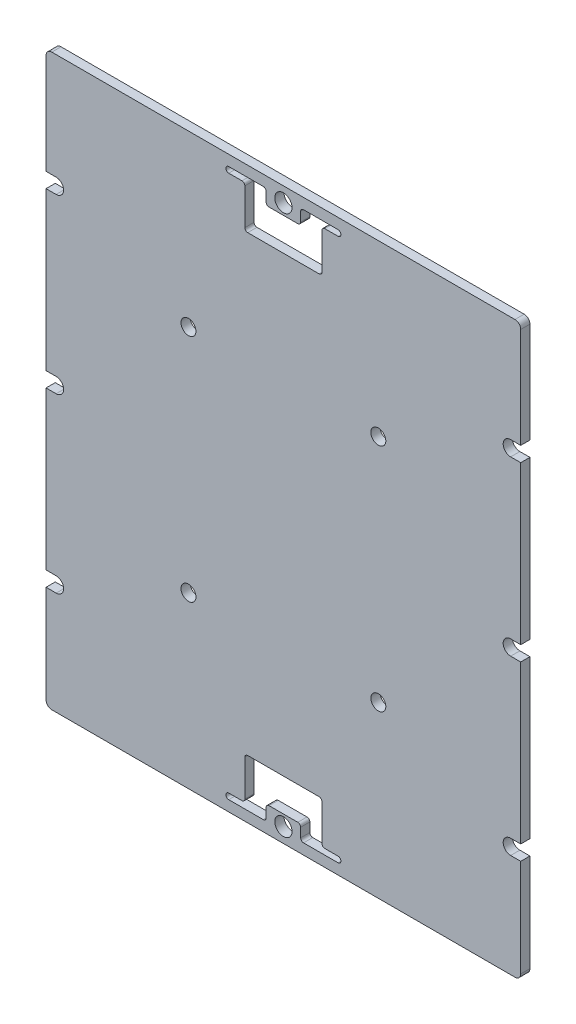
SolidWorks part; units mm, degrees
material "FR4_stuffedProtoboard"
ref_plane "Front Plane" through (0, 0, 0) normal (0, 0, 1) x (1, 0, 0)
ref_plane "Top Plane" through (0, 0, 0) normal (0, 1, 0) x (1, 0, 0)
ref_plane "Right Plane" through (0, 0, 0) normal (1, 0, 0) x (0, 0, -1)
sketch "Sketch2" plane through (0, 0, 0) normal (0, 0, 1) x (1, 0, 0)
  line L0 (39.5, 49.75) -> (-39.5, 49.75) construction
  line L1 (-41.5, 49.75) -> (41.5, 49.75) construction
  line L2 (-41.5, 49.75) -> (-41.5, -49.75) construction
  line L3 (-41.5, -49.75) -> (41.5, -49.75) construction
  line L4 (41.5, 49.75) -> (41.5, -49.75) construction
  line L5 (-41.5, 49.75) -> (41.5, -49.75) construction
  line L6 (-41.5, -49.75) -> (41.5, 49.75) construction
  line L7 (41.5, 51.75) -> (41.5, 40.35) construction
  line L8 (-41.5, 49.75) -> (41.5, 49.75) construction
  line L9 (41.5, 49.75) -> (41.5, -49.75) construction
  line L10 (-41.5, -49.75) -> (41.5, -49.75) construction
  line L11 (-41.5, 49.75) -> (-41.5, -49.75) construction
  line L12 (-37, -31.85) -> (37, -31.85) construction
  line L13 (-37, -30.25) -> (37, -30.25) construction
  line L14 (-37, -21.85) -> (37, -21.85) construction
  line L15 (-37, -20.25) -> (37, -20.25) construction
  line L16 (-37, -11.85) -> (37, -11.85) construction
  line L17 (-37, -10.25) -> (37, -10.25) construction
  line L18 (-37, -1.85) -> (37, -1.85) construction
  line L19 (-37, -0.25) -> (37, -0.25) construction
  line L20 (-37, 8.15) -> (37, 8.15) construction
  line L21 (-37, 9.75) -> (37, 9.75) construction
  line L22 (-37, 18.15) -> (37, 18.15) construction
  line L23 (-37, 19.75) -> (37, 19.75) construction
  line L24 (-37, 28.15) -> (37, 28.15) construction
  line L25 (-37, 29.75) -> (37, 29.75) construction
  line L26 (-37, 38.15) -> (37, 38.15) construction
  line L27 (-37, 39.75) -> (37, 39.75) construction
  line L28 (-37, -31.85) -> (37, -31.85) construction
  line L29 (-37, -30.25) -> (37, -30.25) construction
  line L30 (-37, -21.85) -> (37, -21.85) construction
  line L31 (-37, -20.25) -> (37, -20.25) construction
  line L32 (-37, -11.85) -> (37, -11.85) construction
  line L33 (-37, -10.25) -> (37, -10.25) construction
  line L34 (-37, -1.85) -> (37, -1.85) construction
  line L35 (-37, -0.25) -> (37, -0.25) construction
  line L36 (-37, 8.15) -> (37, 8.15) construction
  line L37 (-37, 9.75) -> (37, 9.75) construction
  line L38 (-37, 18.15) -> (37, 18.15) construction
  line L39 (-37, 19.75) -> (37, 19.75) construction
  line L40 (-37, 28.15) -> (37, 28.15) construction
  line L41 (-37, 29.75) -> (37, 29.75) construction
  line L42 (-37, 38.15) -> (37, 38.15) construction
  line L43 (-37, 39.75) -> (37, 39.75) construction
  line L44 (-37, -40.25) -> (37, -40.25) construction
  line L45 (-37, -41.85) -> (37, -41.85) construction
  line L46 (-41.5, 51.75) -> (-41.5, 40.35) construction
  line L47 (39.5, -49.75) -> (-39.5, -49.75) construction
  line L48 (41.5, -31.9) -> (41.5, -51.75) construction
  line L49 (-41.25, 49.5) -> (41.25, 49.5)
  line L50 (41.25, 49.5) -> (41.25, -49.5)
  line L51 (-41.25, -49.5) -> (41.25, -49.5)
  line L52 (-41.25, 49.5) -> (-41.25, -49.5)
  circle A0 centre (0, 46.95) radius 1.5 construction
  circle A1 centre (0, 46.95) radius 0.8 construction
  circle A2 centre (0, 46.95) radius 1.5 construction
  circle A3 centre (0, 46.95) radius 0.8
  circle A4 centre (-39.5, -30.25) radius 0.8 construction
  circle A5 centre (-39.5, -0.25) radius 0.8 construction
  circle A6 centre (-39.5, 29.75) radius 0.8 construction
  circle A7 centre (-39.5, -30.25) radius 0.8
  circle A8 centre (-39.5, -0.25) radius 0.8
  circle A9 centre (-39.5, 29.75) radius 0.8
  circle A10 centre (39.5, -30.25) radius 0.8 construction
  circle A11 centre (39.5, -0.25) radius 0.8 construction
  circle A12 centre (39.5, 29.75) radius 0.8 construction
  circle A13 centre (39.5, -30.25) radius 0.8
  circle A14 centre (39.5, -0.25) radius 0.8
  circle A15 centre (39.5, 29.75) radius 0.8
  circle A16 centre (0, -46.95) radius 0.8 construction
  circle A17 centre (0, -46.95) radius 0.8
  circle A18 centre (0, -46.95) radius 1.5 construction
  circle A19 centre (0, -46.95) radius 1.5
  circle A20 centre (-16.5, 20) radius 1.75 construction
  circle A21 centre (-16.5, 20) radius 0.8 construction
  circle A22 centre (-16.5, 20) radius 1.75 construction
  circle A23 centre (-16.5, 20) radius 0.8
  circle A24 centre (16.5, 20) radius 1.75 construction
  circle A25 centre (16.5, 20) radius 0.8 construction
  circle A26 centre (16.5, 20) radius 1.75 construction
  circle A27 centre (16.5, 20) radius 0.8
  circle A28 centre (16.5, -20) radius 1.75 construction
  circle A29 centre (-16.5, -20) radius 1.75 construction
  circle A30 centre (16.5, -20) radius 1.75 construction
  circle A31 centre (-16.5, -20) radius 1.75 construction
  circle A32 centre (-16.5, -20) radius 0.8 construction
  circle A33 centre (-16.5, -20) radius 0.8
  circle A34 centre (16.5, -20) radius 0.8 construction
  circle A35 centre (16.5, -20) radius 0.8
  point P0 (0, 0)
  point P74 (0, -40.25)
  point P75 (0, -31.85)
  point P76 (0, -41.85)
  dimension "D2" = 10
  dimension "D3" = 1.6
  dimension "D1" = 0.25
extrude "pcb extrude" add sketch "Sketch2" along normal mid plane 1.6 contours L4 L1 L2 L3 A2 | A2 A3 | L2 L1 L4 L3 region at (0, 0.0296, 0)
sketch "connector locations" plane through (0, 0, 0.8) normal (0, 0, 1) x (1, 0, 0)
  line L0 (34.5, 45.75) -> (4.5, 45.75) construction
  line L1 (-2.5, 44.75) -> (2.5, 44.75) construction
  line L2 (-4.5, 45.75) -> (-34.5, 45.75) construction
  line L3 (34.5, 45.75) -> (4.5, 45.75)
  line L4 (-2.5, 44.75) -> (2.5, 44.75)
  line L5 (-4.5, 45.75) -> (-34.5, 45.75)
  line L6 (-37, 43.25) -> (-37, -43.25) construction
  line L7 (-37, 43.25) -> (-37, -43.25)
  line L8 (37, -43.25) -> (37, 43.25) construction
  line L9 (37, -43.25) -> (37, 43.25)
  line L10 (4.5, -45.75) -> (34.5, -45.75) construction
  line L11 (4.5, -45.75) -> (34.5, -45.75)
  line L12 (-34.5, -45.75) -> (-4.5, -45.75) construction
  line L13 (-2.5, -44.75) -> (2.5, -44.75) construction
  line L14 (-34.5, -45.75) -> (-4.5, -45.75)
  line L15 (-2.5, -44.75) -> (2.5, -44.75)
  line L16 (-37, 39.75) -> (37, 39.75) construction
  line L17 (-33.9182, 41.909) -> (-9.2802, 41.909)
  line L18 (-33.9182, 41.909) -> (-33.9182, 43.306)
  line L19 (-33.9182, 43.306) -> (-9.2802, 43.306)
  line L20 (-9.2802, 41.909) -> (-9.2802, 43.306)
  line L21 (-33.9182, 41.909) -> (-9.2802, 43.306) construction
  line L22 (-33.9182, 43.306) -> (-9.2802, 41.909) construction
  line L23 (-33.9182, 33.306) -> (-22.0818, 33.306)
  line L24 (-33.9182, 33.306) -> (-33.9182, 31.909)
  line L25 (-33.9182, 31.909) -> (-22.0818, 31.909)
  line L26 (-22.0818, 33.306) -> (-22.0818, 31.909)
  line L27 (-33.9182, 33.306) -> (-22.0818, 31.909) construction
  line L28 (-33.9182, 31.909) -> (-22.0818, 33.306) construction
  line L29 (-12.319, 33.306) -> (12.319, 33.306)
  line L30 (-12.319, 33.306) -> (-12.319, 31.909)
  line L31 (-12.319, 31.909) -> (12.319, 31.909)
  line L32 (12.319, 33.306) -> (12.319, 31.909)
  line L33 (-12.319, 33.306) -> (12.319, 31.909) construction
  line L34 (-12.319, 31.909) -> (12.319, 33.306) construction
  line L35 (-33.9182, 23.306) -> (-22.0818, 23.306)
  line L36 (-33.9182, 23.306) -> (-33.9182, 21.909)
  line L37 (-33.9182, 21.909) -> (-22.0818, 21.909)
  line L38 (-33.9182, 23.306) -> (-22.0818, 21.909) construction
  line L39 (-33.9182, 21.909) -> (-22.0818, 23.306) construction
  line L40 (-22.0818, 23.306) -> (-22.0818, 21.909)
  line L41 (-12.319, 23.306) -> (-12.319, 21.909)
  line L42 (-12.319, 23.306) -> (12.319, 23.306)
  line L43 (-12.319, 21.909) -> (12.319, 21.909)
  line L44 (-12.319, 23.306) -> (12.319, 21.909) construction
  line L45 (-12.319, 21.909) -> (12.319, 23.306) construction
  line L46 (12.319, 23.306) -> (12.319, 21.909)
  line L47 (-33.9182, 13.306) -> (-22.0818, 13.306)
  line L48 (-33.9182, 13.306) -> (-33.9182, 11.909)
  line L49 (-33.9182, 11.909) -> (-22.0818, 11.909)
  line L50 (-33.9182, 13.306) -> (-22.0818, 11.909) construction
  line L51 (-33.9182, 11.909) -> (-22.0818, 13.306) construction
  line L52 (-22.0818, 13.306) -> (-22.0818, 11.909)
  line L53 (-12.319, 13.306) -> (-12.319, 11.909)
  line L54 (-12.319, 13.306) -> (12.319, 13.306)
  line L55 (-12.319, 11.909) -> (12.319, 11.909)
  line L56 (-12.319, 13.306) -> (12.319, 11.909) construction
  line L57 (-12.319, 11.909) -> (12.319, 13.306) construction
  line L58 (12.319, 13.306) -> (12.319, 11.909)
  line L59 (-33.9182, 3.306) -> (-22.0818, 3.306)
  line L60 (-33.9182, 3.306) -> (-33.9182, 1.909)
  line L61 (-33.9182, 1.909) -> (-22.0818, 1.909)
  line L62 (-33.9182, 3.306) -> (-22.0818, 1.909) construction
  line L63 (-33.9182, 1.909) -> (-22.0818, 3.306) construction
  line L64 (-22.0818, 3.306) -> (-22.0818, 1.909)
  line L65 (-12.319, 3.306) -> (-12.319, 1.909)
  line L66 (-12.319, 3.306) -> (12.319, 3.306)
  line L67 (-12.319, 1.909) -> (12.319, 1.909)
  line L68 (-12.319, 3.306) -> (12.319, 1.909) construction
  line L69 (-12.319, 1.909) -> (12.319, 3.306) construction
  line L70 (12.319, 3.306) -> (12.319, 1.909)
  line L71 (-33.9182, -6.694) -> (-22.0818, -6.694)
  line L72 (-33.9182, -6.694) -> (-33.9182, -8.091)
  line L73 (-33.9182, -8.091) -> (-22.0818, -8.091)
  line L74 (-33.9182, -6.694) -> (-22.0818, -8.091) construction
  line L75 (-33.9182, -8.091) -> (-22.0818, -6.694) construction
  line L76 (-22.0818, -6.694) -> (-22.0818, -8.091)
  line L77 (-12.319, -6.694) -> (-12.319, -8.091)
  line L78 (-12.319, -6.694) -> (12.319, -6.694)
  line L79 (-12.319, -8.091) -> (12.319, -8.091)
  line L80 (-12.319, -6.694) -> (12.319, -8.091) construction
  line L81 (-12.319, -8.091) -> (12.319, -6.694) construction
  line L82 (12.319, -6.694) -> (12.319, -8.091)
  line L83 (-33.9182, -16.694) -> (-22.0818, -16.694)
  line L84 (-33.9182, -16.694) -> (-33.9182, -18.091)
  line L85 (-33.9182, -18.091) -> (-22.0818, -18.091)
  line L86 (-33.9182, -16.694) -> (-22.0818, -18.091) construction
  line L87 (-33.9182, -18.091) -> (-22.0818, -16.694) construction
  line L88 (-22.0818, -16.694) -> (-22.0818, -18.091)
  line L89 (-12.319, -16.694) -> (-12.319, -18.091)
  line L90 (-12.319, -16.694) -> (12.319, -16.694)
  line L91 (-12.319, -18.091) -> (12.319, -18.091)
  line L92 (-12.319, -16.694) -> (12.319, -18.091) construction
  line L93 (-12.319, -18.091) -> (12.319, -16.694) construction
  line L94 (12.319, -16.694) -> (12.319, -18.091)
  line L95 (-33.9182, -26.694) -> (-22.0818, -26.694)
  line L96 (-33.9182, -26.694) -> (-33.9182, -28.091)
  line L97 (-33.9182, -28.091) -> (-22.0818, -28.091)
  line L98 (-33.9182, -26.694) -> (-22.0818, -28.091) construction
  line L99 (-33.9182, -28.091) -> (-22.0818, -26.694) construction
  line L100 (-22.0818, -26.694) -> (-22.0818, -28.091)
  line L101 (-12.319, -26.694) -> (-12.319, -28.091)
  line L102 (-12.319, -26.694) -> (12.319, -26.694)
  line L103 (-12.319, -28.091) -> (12.319, -28.091)
  line L104 (-12.319, -26.694) -> (12.319, -28.091) construction
  line L105 (-12.319, -28.091) -> (12.319, -26.694) construction
  line L106 (12.319, -26.694) -> (12.319, -28.091)
  line L111 (-35.52, -38.1) -> (-10.98, -38.1)
  line L116 (-35.52, -38.1) -> (-35.52, -37.9)
  line L117 (-35.52, -37.9) -> (-10.98, -37.9)
  line L119 (0, 32.6075) -> (0, 22.6075) construction
  line L120 (-37, 29.75) -> (37, 29.75) construction
  line L121 (32.92, 41.02) -> (35.08, 38.84) construction
  line L122 (32.92, 38.84) -> (35.08, 41.02) construction
  line L123 (26.92, 38.84) -> (29.08, 41.02) construction
  line L124 (26.92, 41.02) -> (29.08, 38.84) construction
  line L125 (20.92, 38.84) -> (23.08, 41.02) construction
  line L126 (20.92, 41.02) -> (23.08, 38.84) construction
  line L127 (26.92, 28.84) -> (29.08, 31.02) construction
  line L128 (26.92, 31.02) -> (29.08, 28.84) construction
  line L129 (20.92, 28.84) -> (23.08, 31.02) construction
  line L130 (20.92, 31.02) -> (23.08, 28.84) construction
  line L131 (26.92, 18.84) -> (29.08, 21.02) construction
  line L132 (26.92, 21.02) -> (29.08, 18.84) construction
  line L133 (20.92, 18.84) -> (23.08, 21.02) construction
  line L134 (20.92, 21.02) -> (23.08, 18.84) construction
  line L135 (26.92, 8.84) -> (29.08, 11.02) construction
  line L136 (26.92, 11.02) -> (29.08, 8.84) construction
  line L137 (20.92, 8.84) -> (23.08, 11.02) construction
  line L138 (20.92, 11.02) -> (23.08, 8.84) construction
  line L139 (26.92, -1.16) -> (29.08, 1.02) construction
  line L140 (26.92, 1.02) -> (29.08, -1.16) construction
  line L141 (20.92, -1.16) -> (23.08, 1.02) construction
  line L142 (20.92, 1.02) -> (23.08, -1.16) construction
  line L143 (26.92, -11.16) -> (29.08, -8.98) construction
  line L144 (26.92, -8.98) -> (29.08, -11.16) construction
  line L145 (20.92, -11.16) -> (23.08, -8.98) construction
  line L146 (20.92, -8.98) -> (23.08, -11.16) construction
  line L147 (26.92, -21.16) -> (29.08, -18.98) construction
  line L148 (26.92, -18.98) -> (29.08, -21.16) construction
  line L149 (20.92, -21.16) -> (23.08, -18.98) construction
  line L150 (20.92, -18.98) -> (23.08, -21.16) construction
  line L151 (26.92, -31.16) -> (29.08, -28.98) construction
  line L152 (26.92, -28.98) -> (29.08, -31.16) construction
  line L153 (20.92, -31.16) -> (23.08, -28.98) construction
  line L154 (20.92, -28.98) -> (23.08, -31.16) construction
  line L155 (26.92, -41.16) -> (29.08, -38.98) construction
  line L156 (26.92, -38.98) -> (29.08, -41.16) construction
  line L157 (20.92, -41.16) -> (23.08, -38.98) construction
  line L158 (20.92, -38.98) -> (23.08, -41.16) construction
  line L159 (32.92, 28.84) -> (35.08, 31.02) construction
  line L160 (32.92, 31.02) -> (35.08, 28.84) construction
  line L161 (32.92, 18.84) -> (35.08, 21.02) construction
  line L162 (32.92, 21.02) -> (35.08, 18.84) construction
  line L163 (32.92, 8.84) -> (35.08, 11.02) construction
  line L164 (32.92, 11.02) -> (35.08, 8.84) construction
  line L165 (32.92, -1.16) -> (35.08, 1.02) construction
  line L166 (32.92, 1.02) -> (35.08, -1.16) construction
  line L167 (32.92, -11.16) -> (35.08, -8.98) construction
  line L168 (32.92, -8.98) -> (35.08, -11.16) construction
  line L169 (32.92, -21.16) -> (35.08, -18.98) construction
  line L170 (32.92, -18.98) -> (35.08, -21.16) construction
  line L171 (32.92, -31.16) -> (35.08, -28.98) construction
  line L172 (32.92, -28.98) -> (35.08, -31.16) construction
  line L173 (32.92, -41.16) -> (35.08, -38.98) construction
  line L174 (32.92, -38.98) -> (35.08, -41.16) construction
  line L175 (34, 39.93) -> (28, 39.93) construction
  line L176 (34, 39.93) -> (34, 29.93) construction
  line L177 (-36.51, -37.5) -> (-36.51, -46.51)
  line L178 (-36.51, -46.51) -> (-9.99, -46.51)
  line L179 (-9.99, -46.51) -> (-9.99, -37.5)
  line L180 (-41.25, -49.5) -> (41.25, -49.5) construction
  line L181 (-41.25, 49.5) -> (-41.25, -49.5) construction
  line L182 (-10.98, -38.1) -> (-10.98, -37.9)
  line L183 (-35.52, -38.1) -> (-10.98, -37.9) construction
  line L184 (-35.52, -37.9) -> (-10.98, -38.1) construction
  arc A0 (4.5, 45.75) -> (2.5, 44.75) centre (4.5, 43.25) ccw construction
  arc A1 (-2.5, 44.75) -> (-4.5, 45.75) centre (-4.5, 43.25) ccw construction
  arc A2 (-34.5, 45.75) -> (-37, 43.25) centre (-34.5, 43.25) ccw construction
  arc A3 (4.5, 45.75) -> (2.5, 44.75) centre (4.5, 43.25) ccw
  arc A4 (-2.5, 44.75) -> (-4.5, 45.75) centre (-4.5, 43.25) ccw
  arc A5 (-34.5, 45.75) -> (-37, 43.25) centre (-34.5, 43.25) ccw
  arc A6 (37, 43.25) -> (34.5, 45.75) centre (34.5, 43.25) ccw construction
  arc A7 (37, 43.25) -> (34.5, 45.75) centre (34.5, 43.25) ccw
  arc A8 (34.5, -45.75) -> (37, -43.25) centre (34.5, -43.25) ccw construction
  arc A9 (34.5, -45.75) -> (37, -43.25) centre (34.5, -43.25) ccw
  arc A10 (-37, -43.25) -> (-34.5, -45.75) centre (-34.5, -43.25) ccw construction
  arc A11 (-4.5, -45.75) -> (-2.5, -44.75) centre (-4.5, -43.25) ccw construction
  arc A12 (2.5, -44.75) -> (4.5, -45.75) centre (4.5, -43.25) ccw construction
  arc A13 (-37, -43.25) -> (-34.5, -45.75) centre (-34.5, -43.25) ccw
  arc A14 (-4.5, -45.75) -> (-2.5, -44.75) centre (-4.5, -43.25) ccw
  arc A15 (2.5, -44.75) -> (4.5, -45.75) centre (4.5, -43.25) ccw
  circle A16 centre (-21.5992, 42.6075) radius 0.5
  circle A17 centre (0, 32.6075) radius 0.5
  circle A18 centre (-28, 32.6075) radius 0.5
  circle A19 centre (-28, 22.6075) radius 0.5
  circle A20 centre (0, 22.6075) radius 0.5
  circle A21 centre (-28, 12.6075) radius 0.5
  circle A22 centre (0, 12.6075) radius 0.5
  circle A23 centre (-28, 2.6075) radius 0.5
  circle A24 centre (0, 2.6075) radius 0.5
  circle A25 centre (-28, -7.3925) radius 0.5
  circle A26 centre (0, -7.3925) radius 0.5
  circle A27 centre (-28, -17.3925) radius 0.5
  circle A28 centre (0, -17.3925) radius 0.5
  circle A29 centre (-28, -27.3925) radius 0.5
  circle A30 centre (0, -27.3925) radius 0.5
  circle A33 centre (35.08, 41.02) radius 0.32
  circle A34 centre (32.92, 38.84) radius 0.32
  circle A35 centre (35.08, 38.84) radius 0.32
  circle A36 centre (32.92, 41.02) radius 0.32
  circle A37 centre (26.92, 41.02) radius 0.32
  circle A38 centre (29.08, 41.02) radius 0.32
  circle A39 centre (26.92, 38.84) radius 0.32
  circle A40 centre (29.08, 38.84) radius 0.32
  circle A41 centre (20.92, 41.02) radius 0.32
  circle A42 centre (23.08, 41.02) radius 0.32
  circle A43 centre (20.92, 38.84) radius 0.32
  circle A44 centre (23.08, 38.84) radius 0.32
  circle A45 centre (26.92, 31.02) radius 0.32
  circle A46 centre (29.08, 31.02) radius 0.32
  circle A47 centre (26.92, 28.84) radius 0.32
  circle A48 centre (29.08, 28.84) radius 0.32
  circle A49 centre (20.92, 31.02) radius 0.32
  circle A50 centre (23.08, 31.02) radius 0.32
  circle A51 centre (20.92, 28.84) radius 0.32
  circle A52 centre (23.08, 28.84) radius 0.32
  circle A53 centre (26.92, 21.02) radius 0.32
  circle A54 centre (29.08, 21.02) radius 0.32
  circle A55 centre (26.92, 18.84) radius 0.32
  circle A56 centre (29.08, 18.84) radius 0.32
  circle A57 centre (20.92, 21.02) radius 0.32
  circle A58 centre (23.08, 21.02) radius 0.32
  circle A59 centre (20.92, 18.84) radius 0.32
  circle A60 centre (23.08, 18.84) radius 0.32
  circle A61 centre (26.92, 11.02) radius 0.32
  circle A62 centre (29.08, 11.02) radius 0.32
  circle A63 centre (26.92, 8.84) radius 0.32
  circle A64 centre (29.08, 8.84) radius 0.32
  circle A65 centre (20.92, 11.02) radius 0.32
  circle A66 centre (23.08, 11.02) radius 0.32
  circle A67 centre (20.92, 8.84) radius 0.32
  circle A68 centre (23.08, 8.84) radius 0.32
  circle A69 centre (26.92, 1.02) radius 0.32
  circle A70 centre (29.08, 1.02) radius 0.32
  circle A71 centre (26.92, -1.16) radius 0.32
  circle A72 centre (29.08, -1.16) radius 0.32
  circle A73 centre (20.92, 1.02) radius 0.32
  circle A74 centre (23.08, 1.02) radius 0.32
  circle A75 centre (20.92, -1.16) radius 0.32
  circle A76 centre (23.08, -1.16) radius 0.32
  circle A77 centre (26.92, -8.98) radius 0.32
  circle A78 centre (29.08, -8.98) radius 0.32
  circle A79 centre (26.92, -11.16) radius 0.32
  circle A80 centre (29.08, -11.16) radius 0.32
  circle A81 centre (20.92, -8.98) radius 0.32
  circle A82 centre (23.08, -8.98) radius 0.32
  circle A83 centre (20.92, -11.16) radius 0.32
  circle A84 centre (23.08, -11.16) radius 0.32
  circle A85 centre (26.92, -18.98) radius 0.32
  circle A86 centre (29.08, -18.98) radius 0.32
  circle A87 centre (26.92, -21.16) radius 0.32
  circle A88 centre (29.08, -21.16) radius 0.32
  circle A89 centre (20.92, -18.98) radius 0.32
  circle A90 centre (23.08, -18.98) radius 0.32
  circle A91 centre (20.92, -21.16) radius 0.32
  circle A92 centre (23.08, -21.16) radius 0.32
  circle A93 centre (26.92, -28.98) radius 0.32
  circle A94 centre (29.08, -28.98) radius 0.32
  circle A95 centre (26.92, -31.16) radius 0.32
  circle A96 centre (29.08, -31.16) radius 0.32
  circle A97 centre (20.92, -28.98) radius 0.32
  circle A98 centre (23.08, -28.98) radius 0.32
  circle A99 centre (20.92, -31.16) radius 0.32
  circle A100 centre (23.08, -31.16) radius 0.32
  circle A101 centre (26.92, -38.98) radius 0.32
  circle A102 centre (29.08, -38.98) radius 0.32
  circle A103 centre (26.92, -41.16) radius 0.32
  circle A104 centre (29.08, -41.16) radius 0.32
  circle A105 centre (20.92, -38.98) radius 0.32
  circle A106 centre (23.08, -38.98) radius 0.32
  circle A107 centre (20.92, -41.16) radius 0.32
  circle A108 centre (23.08, -41.16) radius 0.32
  circle A109 centre (32.92, 31.02) radius 0.32
  circle A110 centre (35.08, 31.02) radius 0.32
  circle A111 centre (32.92, 28.84) radius 0.32
  circle A112 centre (35.08, 28.84) radius 0.32
  circle A113 centre (32.92, 21.02) radius 0.32
  circle A114 centre (35.08, 21.02) radius 0.32
  circle A115 centre (32.92, 18.84) radius 0.32
  circle A116 centre (35.08, 18.84) radius 0.32
  circle A117 centre (32.92, 11.02) radius 0.32
  circle A118 centre (35.08, 11.02) radius 0.32
  circle A119 centre (32.92, 8.84) radius 0.32
  circle A120 centre (35.08, 8.84) radius 0.32
  circle A121 centre (32.92, 1.02) radius 0.32
  circle A122 centre (35.08, 1.02) radius 0.32
  circle A123 centre (32.92, -1.16) radius 0.32
  circle A124 centre (35.08, -1.16) radius 0.32
  circle A125 centre (32.92, -8.98) radius 0.32
  circle A126 centre (35.08, -8.98) radius 0.32
  circle A127 centre (32.92, -11.16) radius 0.32
  circle A128 centre (35.08, -11.16) radius 0.32
  circle A129 centre (32.92, -18.98) radius 0.32
  circle A130 centre (35.08, -18.98) radius 0.32
  circle A131 centre (32.92, -21.16) radius 0.32
  circle A132 centre (35.08, -21.16) radius 0.32
  circle A133 centre (32.92, -28.98) radius 0.32
  circle A134 centre (35.08, -28.98) radius 0.32
  circle A135 centre (32.92, -31.16) radius 0.32
  circle A136 centre (35.08, -31.16) radius 0.32
  circle A137 centre (32.92, -38.98) radius 0.32
  circle A138 centre (35.08, -38.98) radius 0.32
  circle A139 centre (32.92, -41.16) radius 0.32
  circle A140 centre (35.08, -41.16) radius 0.32
  point P18 (-21.5992, 42.6075)
  point P29 (-28, 32.6075)
  point P34 (0, 32.6075)
  point P50 (-28, 22.6075)
  point P55 (0, 22.6075)
  point P64 (-28, 12.6075)
  point P69 (0, 12.6075)
  point P78 (-28, 2.6075)
  point P83 (0, 2.6075)
  point P92 (-28, -7.3925)
  point P97 (0, -7.3925)
  point P106 (-28, -17.3925)
  point P111 (0, -17.3925)
  point P120 (-28, -27.3925)
  point P125 (0, -27.3925)
  point P134 (-23.25, -38)
  point P135 (-23.25, -46.51)
  point P136 (-23.25, -38)
  point P165 (34, 39.93)
  point P170 (28, 39.93)
  point P179 (22, 39.93)
  point P188 (28, 29.93)
  point P197 (22, 29.93)
  point P206 (28, 19.93)
  point P215 (22, 19.93)
  point P224 (28, 9.93)
  point P233 (22, 9.93)
  point P242 (28, -0.07)
  point P251 (22, -0.07)
  point P260 (28, -10.07)
  point P269 (22, -10.07)
  point P278 (28, -20.07)
  point P287 (22, -20.07)
  point P296 (28, -30.07)
  point P305 (22, -30.07)
  point P314 (28, -40.07)
  point P323 (22, -40.07)
  point P332 (34, 29.93)
  point P341 (34, 19.93)
  point P350 (34, 9.93)
  point P359 (34, -0.07)
  point P368 (34, -10.07)
  point P377 (34, -20.07)
  point P386 (34, -30.07)
  point P395 (34, -40.07)
  dimension "D4" = 1
  dimension "D5" = 11.8364
  dimension "D10" = 0.64
  dimension "D1" = 24.638
  dimension "D2" = 1.397
  dimension "D3" = 2.159
  dimension "D6" = 28
  dimension "D8" = 10
  dimension "D9" = 2.159
  dimension "D11" = 2.18
  dimension "D12" = 2.16
  dimension "D13" = 0.18
  dimension "D14" = 34
  dimension "D17" = 6
  dimension "D18" = 10
  dimension "D19" = 2.99
  dimension "D20" = 4.74
  dimension "D21" = 26.52
  dimension "D22" = 9.01
  dimension "D23" = 8.51
  dimension "D24" = 24.54
  dimension "D25" = 0.2
  dimension "D7" = 7
  dimension "D15" = 3
  dimension "D16" = 9
fillet "corner fillets" radius 1 4 edges at (41.25, -49.5, 0) (-41.25, -49.5, 0) (41.25, 49.5, 0) (-41.25, 49.5, 0)
sketch "Sketch4" plane through (0, 0, 0.8) normal (0, 0, 1) x (1, 0, 0)
  line L0 (0, 46.95) -> (0, 39.35) construction
  line L1 (6.7, 39.35) -> (-6.7, 39.35)
  line L2 (-6.7, 39.35) -> (-6.7, 46.65)
  line L3 (-6.7, 46.65) -> (-9.5, 46.65)
  line L4 (-4.5, 45.75) -> (-34.5, 45.75) construction
  line L5 (-9.5, 47.65) -> (-3, 47.65)
  line L6 (-3, 47.65) -> (-3, 45.05)
  line L7 (-3, 45.05) -> (3, 45.05)
  line L8 (3, 47.65) -> (3, 45.05)
  line L9 (6.7, 39.35) -> (6.7, 46.65)
  line L10 (6.7, 46.65) -> (9.5, 46.65)
  line L11 (9.5, 47.65) -> (3, 47.65)
  line L12 (0.88, 0) -> (-0.88, 0) construction
  line L13 (6.7, -46.65) -> (9.5, -46.65)
  line L14 (9.5, -47.65) -> (3, -47.65)
  line L15 (3, -47.65) -> (3, -45.05)
  line L16 (-3, -45.05) -> (3, -45.05)
  line L17 (-3, -47.65) -> (-3, -45.05)
  line L18 (-9.5, -47.65) -> (-3, -47.65)
  line L19 (-6.7, -46.65) -> (-9.5, -46.65)
  line L20 (-6.7, -39.35) -> (-6.7, -46.65)
  line L21 (6.7, -39.35) -> (-6.7, -39.35)
  line L22 (6.7, -39.35) -> (6.7, -46.65)
  arc A0 (-9.5, 47.65) -> (-9.5, 46.65) centre (-9.5, 47.15) ccw
  arc A1 (9.5, 47.65) -> (9.5, 46.65) centre (9.5, 47.15) cw
  circle A2 centre (0, 46.95) radius 1.5
  arc A3 (9.5, -47.65) -> (9.5, -46.65) centre (9.5, -47.15) ccw
  arc A4 (-9.5, -47.65) -> (-9.5, -46.65) centre (-9.5, -47.15) cw
  point P17 (0, 45.05)
  dimension "D3" = 1
  dimension "D8" = 3
  dimension "D1" = 3
  dimension "D2" = 9.5
  dimension "D4" = 0.9
  dimension "D5" = 7.3
  dimension "D6" = 2.6
  dimension "D7" = 3.7
extrude "solar holes" cut sketch "Sketch4" against normal through all
fillet "solar hole fillets" radius 0.5 16 edges at (6.7, 46.65, 0) (3, 47.65, 0) (3, 45.05, 0) (6.7, 39.35, 0) (-6.7, 39.35, 0) (-6.7, 46.65, 0) (-3, 45.05, 0) (-3, 47.65, 0) (3, -47.65, 0) (3, -45.05, 0) (-3, -47.65, 0) (-3, -45.05, 0) (-6.7, -46.65, 0) (6.7, -46.65, 0) (6.7, -39.35, 0) (-6.7, -39.35, 0)
sketch "m2 locations" plane through (0, 0, 0.8) normal (0, 0, 1) x (1, 0, 0)
  point P0 (-39.5, 29.75)
  point P1 (-39.5, -0.25)
  point P3 (-39.5, -30.25)
  point P5 (-16.5, -20)
  point P7 (-16.5, 20)
  point P9 (16.5, 20)
  point P11 (16.5, -20)
  point P13 (39.5, -30.25)
  point P15 (39.5, -0.25)
  point P17 (39.5, 29.75)
hole_wizard "M2 Clearance Holes" positions "Sketch8" profile "Sketch9" hole size "M2" standard "ANSI Metric" end condition through all
sketch "Sketch8" plane through (0, 0, 0.8) normal (0, 0, 1) x (1, 0, 0)
  point P0 (-39.5, 29.75)
  point P3 (-39.5, -0.25)
  point P6 (-16.5, 20)
  point P9 (16.5, 20)
  point P12 (16.5, -20)
  point P15 (-16.5, -20)
  point P18 (39.5, 29.75)
  point P21 (39.5, -0.25)
  point P24 (39.5, -30.25)
  point P27 (-39.5, -30.25)
sketch "Sketch9" plane through (-39.5, 29.75, 0.8) normal (1, 0, 0) x (0, -1, 0)
  line L0 (0, 0) -> (0, 1.6)
  line L1 (0, 1.6) -> (1.3, 1.6)
  line L2 (1.3, 1.6) -> (1.3, 0)
  line L5 (1.3, 0) -> (0, 0)
  line L11 (0, -6.35) -> (0, 107.95) construction
  dimension "Thru Hole Dia." = 2.6
  dimension "Thru Hole Depth" = 1.6
sketch "Sketch10" plane through (0, 0, 0.8) normal (0, 0, 1) x (1, 0, 0)
  line L0 (-41.25, 48.5) -> (-41.25, -48.5) construction
  line L1 (-39.5, 31.05) -> (-41.25, 31.05)
  line L2 (-39.5, 31.05) -> (-39.5, 28.45)
  line L3 (-39.5, 28.45) -> (-41.25, 28.45)
  line L4 (-41.25, 31.05) -> (-41.25, 28.45)
  line L5 (41.25, 48.5) -> (41.25, -48.5) construction
  line L6 (-39.5, 1.05) -> (-41.25, 1.05)
  line L7 (-39.5, 1.05) -> (-39.5, -1.55)
  line L8 (-39.5, -1.55) -> (-41.25, -1.55)
  line L9 (-41.25, 1.05) -> (-41.25, -1.55)
  line L10 (-39.5, -28.95) -> (-41.25, -28.95)
  line L11 (-39.5, -28.95) -> (-39.5, -31.55)
  line L12 (-39.5, -31.55) -> (-41.25, -31.55)
  line L13 (-41.25, -28.95) -> (-41.25, -31.55)
  line L14 (39.5, -28.95) -> (41.25, -28.95)
  line L15 (39.5, -28.95) -> (39.5, -31.55)
  line L16 (39.5, -31.55) -> (41.25, -31.55)
  line L17 (41.25, -28.95) -> (41.25, -31.55)
  line L19 (39.5, 1.05) -> (41.25, 1.05)
  line L20 (39.5, 1.05) -> (39.5, -1.55)
  line L21 (39.5, -1.55) -> (41.25, -1.55)
  line L22 (41.25, 1.05) -> (41.25, -1.55)
  line L23 (39.5, 31.05) -> (41.25, 31.05)
  line L24 (39.5, 31.05) -> (39.5, 28.45)
  line L25 (39.5, 28.45) -> (41.25, 28.45)
  line L26 (41.25, 31.05) -> (41.25, 28.45)
  circle A0 centre (-39.5, 29.75) radius 1.3 construction
  circle A1 centre (-39.5, -0.25) radius 1.3 construction
  circle A2 centre (-39.5, -30.25) radius 1.3 construction
  circle A3 centre (39.5, -30.25) radius 1.3 construction
  circle A4 centre (39.5, -0.25) radius 1.3 construction
  circle A5 centre (39.5, 29.75) radius 1.3 construction
  point P43 (-39.5, 29.75)
extrude "Cut-Extrude2" cut sketch "Sketch10" against normal through all
sketch "Solar Board Cutout Locations" plane through (0, 0, 0.8) normal (0, 0, 1) x (1, 0, 0)
  line L1 (-35.5, -8.25) -> (-29.5, -8.25) construction
  line L2 (-29.5, 7.75) -> (-35.5, 7.75) construction
  line L3 (-37.5, 5.75) -> (-37.5, -6.25) construction
  line L4 (-27.5, -6.25) -> (-27.5, 5.75) construction
  line L5 (-35.5, -8.25) -> (-29.5, -8.25)
  line L6 (-29.5, 7.75) -> (-35.5, 7.75)
  line L7 (-37.5, 5.75) -> (-37.5, -6.25)
  line L8 (-27.5, -6.25) -> (-27.5, 5.75)
  line L9 (29.5, -8.25) -> (35.5, -8.25) construction
  line L10 (27.5, 5.75) -> (27.5, -6.25) construction
  line L11 (35.5, 7.75) -> (29.5, 7.75) construction
  line L12 (37.5, -6.25) -> (37.5, 5.75) construction
  line L13 (29.5, -8.25) -> (35.5, -8.25)
  line L14 (27.5, 5.75) -> (27.5, -6.25)
  line L15 (35.5, 7.75) -> (29.5, 7.75)
  line L16 (37.5, -6.25) -> (37.5, 5.75)
  arc A0 (-29.5, -8.25) -> (-27.5, -6.25) centre (-29.5, -6.25) ccw construction
  arc A1 (-37.5, -6.25) -> (-35.5, -8.25) centre (-35.5, -6.25) ccw construction
  arc A2 (-35.5, 7.75) -> (-37.5, 5.75) centre (-35.5, 5.75) ccw construction
  arc A3 (-27.5, 5.75) -> (-29.5, 7.75) centre (-29.5, 5.75) ccw construction
  arc A4 (-29.5, -8.25) -> (-27.5, -6.25) centre (-29.5, -6.25) ccw
  arc A5 (-37.5, -6.25) -> (-35.5, -8.25) centre (-35.5, -6.25) ccw
  arc A6 (-35.5, 7.75) -> (-37.5, 5.75) centre (-35.5, 5.75) ccw
  arc A7 (-27.5, 5.75) -> (-29.5, 7.75) centre (-29.5, 5.75) ccw
  arc A8 (35.5, -8.25) -> (37.5, -6.25) centre (35.5, -6.25) ccw construction
  arc A9 (27.5, -6.25) -> (29.5, -8.25) centre (29.5, -6.25) ccw construction
  arc A10 (29.5, 7.75) -> (27.5, 5.75) centre (29.5, 5.75) ccw construction
  arc A11 (37.5, 5.75) -> (35.5, 7.75) centre (35.5, 5.75) ccw construction
  arc A12 (35.5, -8.25) -> (37.5, -6.25) centre (35.5, -6.25) ccw
  arc A13 (27.5, -6.25) -> (29.5, -8.25) centre (29.5, -6.25) ccw
  arc A14 (29.5, 7.75) -> (27.5, 5.75) centre (29.5, 5.75) ccw
  arc A15 (37.5, 5.75) -> (35.5, 7.75) centre (35.5, 5.75) ccw
